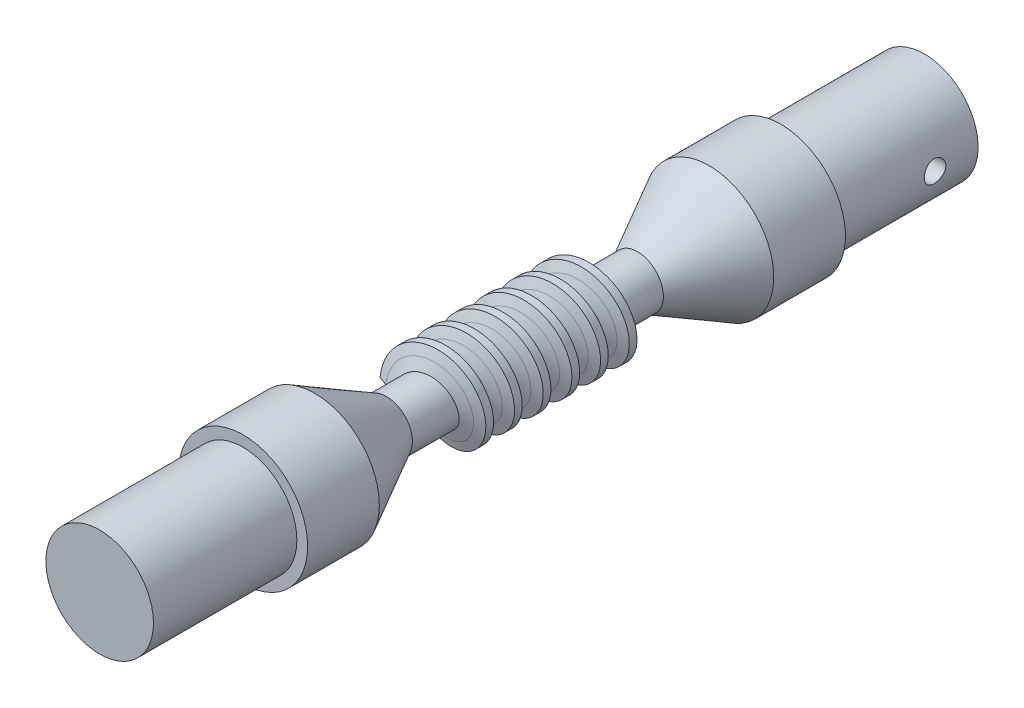
SolidWorks part; units mm, degrees
ref_plane "Front Plane" through (0, 0, 0) normal (0, 0, 1) x (1, 0, 0)
ref_plane "Top Plane" through (0, 0, 0) normal (0, 1, 0) x (1, 0, 0)
ref_plane "Right Plane" through (0, 0, 0) normal (1, 0, 0) x (0, 0, -1)
sketch "Sketch1" plane through (0, 0, 0) normal (0, 0, 1) x (1, 0, 0)
  circle A0 centre (0, 0) radius 3.61
  dimension "D1" = 7.22
extrude "Boss-Extrude1" add sketch "Sketch1" along normal blind 35
ref_plane "Plane2" through (0, 0, 5) normal (0, 0, -1) x (-1, 0, 0)
sketch "Sketch12" plane through (0, 0, 5) normal (0, 0, -1) x (-1, 0, 0)
  circle A0 centre (0, 0) radius 3.61
  dimension "D1" = 7.22
curve "Helix/Spiral4" pitch 4 height 24 radius 3.61 centre (0, 0, 5) axis (0, 0, 1) start towards (-1, 0, 0)
sketch "Sketch13" plane through (0, 0, 0) normal (0, 1, 0) x (1, 0, 0)
  line L0 (-6.36, -5.5378) -> (-6.36, -4.4622)
  line L1 (-5.09, -6) -> (-3.61, -6.5387)
  line L2 (-5.09, -4) -> (-6.36, -4.4622)
  line L4 (-5.09, -6) -> (-6.36, -5.5378)
  line L5 (-5.09, -4) -> (-3.61, -3.4613)
  line L6 (-3.61, -6.5387) -> (-3.61, -3.4613)
  point P2 (-6.36, -5)
  point P8 (-3.61, -5)
  point P9 (-3.61, -5)
sweep "Sweep4" add profiles "Sketch13" path "Helix/Spiral4"
sketch "Sketch23" plane through (0, 0, 0) normal (1, 0, 0) x (0, 0, -1)
  line L0 (-35, 0) -> (-45, 0) construction
  line L1 (-35, 3.61) -> (-35, -3.61) construction
  line L2 (-45, 0) -> (-45, 9)
  line L3 (-45, 9) -> (-35, 3.61)
  line L4 (-35, 3.61) -> (-35, 0)
  line L5 (-35, 0) -> (-45, 0)
revolve "Revolve1" add sketch "Sketch23" angle 360 about L0
sketch "Sketch24" plane through (0, 0, 45) normal (0, 0, 1) x (1, 0, 0)
  circle A0 centre (0, 0) radius 9
extrude "Boss-Extrude6" add sketch "Sketch24" along normal blind 10
sketch "Sketch25" plane through (0, 0, 55) normal (0, 0, 1) x (1, 0, 0)
  circle A0 centre (0, 0) radius 7.5
extrude "Boss-Extrude7" add sketch "Sketch25" along normal blind 20
sketch "Sketch26" plane through (0, 0, 0) normal (1, 0, 0) x (0, 0, -1)
  line L0 (0, 0) -> (10, 0) construction
  line L1 (10, 0) -> (10, 9)
  line L2 (10, 9) -> (0, 3.61)
  line L3 (0, -3.61) -> (0, 3.61) construction
  line L4 (0, 3.61) -> (0, 0)
  line L5 (0, 0) -> (10, 0)
revolve "Revolve2" add sketch "Sketch26" angle 360 about L0
sketch "Sketch27" plane through (0, 0, -10) normal (0, 0, -1) x (-1, 0, 0)
  circle A0 centre (0, 0) radius 9
extrude "Boss-Extrude8" add sketch "Sketch27" along normal blind 10
sketch "Sketch28" plane through (0, 0, -20) normal (0, 0, -1) x (-1, 0, 0)
  circle A0 centre (0, 0) radius 7.5
extrude "Boss-Extrude9" add sketch "Sketch28" along normal blind 20
sketch "Sketch31" plane through (0, 0, -40) normal (0, 0, -1) x (-1, 0, 0)
  circle A0 centre (0, 0) radius 2
extrude "Cut-Extrude2" cut sketch "Sketch31" against normal blind 12
sketch "Sketch32" plane through (0, 0, 0) normal (1, 0, 0) x (0, 0, -1)
  line L0 (40, 0) -> (34, 0) construction
  line L1 (40, -7.5) -> (40, 7.5) construction
  circle A0 centre (34, 0) radius 1.5
extrude "Cut-Extrude3" cut sketch "Sketch32" along normal blind 26 and the other way blind 24
